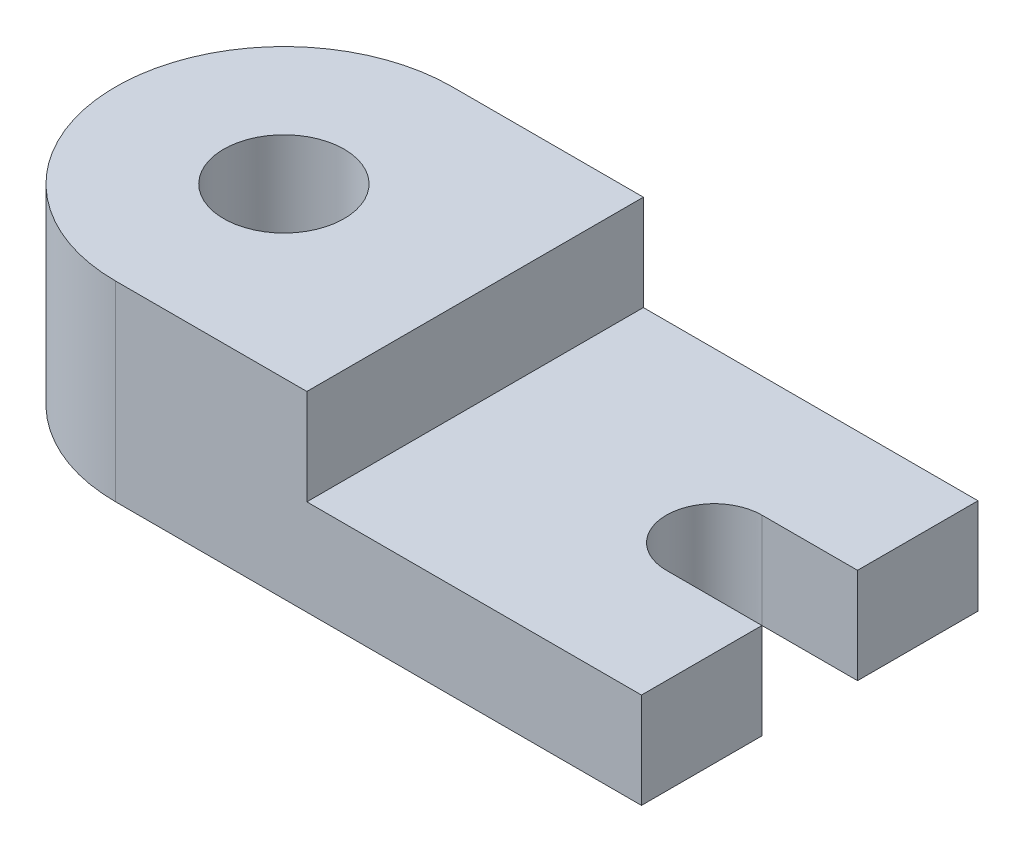
SolidWorks part; units mm, degrees
ref_plane "Alzado" through (0, 0, 0) normal (0, 0, 1) x (1, 0, 0)
ref_plane "Planta" through (0, 0, 0) normal (0, 1, 0) x (1, 0, 0)
ref_plane "Vista lateral" through (0, 0, 0) normal (1, 0, 0) x (0, 0, -1)
sketch "Croquis1" plane through (0, 0, 0) normal (0, 1, 0) x (1, 0, 0)
  line L0 (69.85, -6.35) -> (69.85, -22.352)
  line L1 (0, 22.352) -> (69.85, 22.352)
  line L3 (0, -22.352) -> (69.85, -22.352)
  line L4 (69.85, 22.352) -> (69.85, 6.35)
  line L5 (69.85, 6.35) -> (57.15, 6.35)
  line L7 (69.85, -6.35) -> (57.15, -6.35)
  line L9 (25.4, 22.352) -> (25.4, -22.352)
  arc A0 (0, 22.352) -> (0, -22.352) centre (0, 0) ccw
  circle A1 centre (0, 0) radius 8.001
  arc A2 (57.15, 6.35) -> (57.15, -6.35) centre (57.15, 0) ccw
  dimension "D1" = 25.4
  dimension "D2" = 16.002
  dimension "D5" = 44.704
  dimension "D6" = 6.35
  dimension "D3" = 44.45
  dimension "D4" = 22.352
  dimension "D7" = 12.7
extrude "Saliente-Extruir1" add sketch "Croquis1" along normal blind 31.75 contours L1 A0 L3 L9 A1 region at (12.7, 0, 21.6979)
extrude "Saliente-Extruir2" add sketch "Croquis1<3>" along normal blind 12.7 contours A2 L5 L4 L1 L9 L3 L0 L7 region at (45.9268, 0, 0)
sketch "Croquis1<3>" plane through (0, 0, 0) normal (0, 1, 0) x (1, 0, 0) same geometry as "Croquis1"
sketch "Croquis3" plane through (0, 31.75, 0) normal (0, 1, 0) x (1, 0, 0)
  line L1 (25.4, 22.352) -> (-22.352, 22.352)
  line L2 (25.4, 22.352) -> (25.4, -22.352)
  line L3 (25.4, -22.352) -> (-22.352, -22.352)
  line L4 (-22.352, 22.352) -> (-22.352, -22.352)
  arc A1 (0, 22.352) -> (0, -22.352) centre (0, 0) ccw construction
extrude "Cortar-Extruir4" cut sketch "Croquis3" against normal blind 6.35 contours L3 L4 L1 L2
